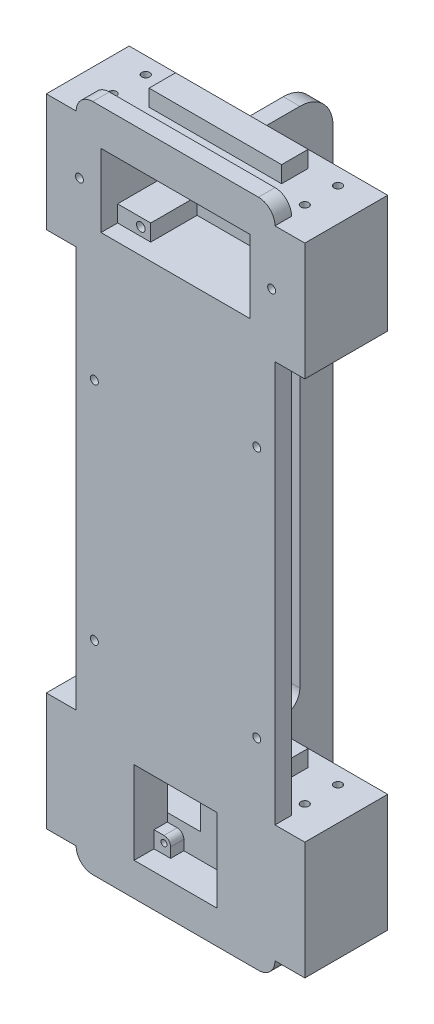
SolidWorks part; units mm, degrees
ref_plane "前视基准面" through (0, 0, 0) normal (0, 0, 1) x (1, 0, 0)
ref_plane "上视基准面" through (0, 0, 0) normal (0, 1, 0) x (1, 0, 0)
ref_plane "右视基准面" through (0, 0, 0) normal (1, 0, 0) x (0, 0, -1)
sketch "草图1" plane through (0, 0, 0) normal (0, 0, 1) x (1, 0, 0)
  line L1 (5, 0) -> (55, 0)
  line L2 (0, -5) -> (0, -197.05)
  line L3 (5, -202.05) -> (55, -202.05)
  line L4 (60, -5) -> (60, -197.05)
  arc A0 (0, -197.05) -> (5, -202.05) centre (5, -197.05) ccw
  arc A1 (55, -202.05) -> (60, -197.05) centre (55, -197.05) ccw
  arc A2 (60, -5) -> (55, 0) centre (55, -5) ccw
  arc A3 (0, -5) -> (5, 0) centre (5, -5) cw
  point P9 (60, -202.05)
  point P12 (60, 0)
  point P15 (0, 0)
  dimension "D3" = 5
  dimension "D1" = 202.05
  dimension "D2" = 60
extrude "凸台-拉伸1" add sketch "草图1" along normal blind 5
sketch "草图3" plane through (0, 0, 5) normal (0, 0, 1) x (1, 0, 0)
  line L0 (60, -101.025) -> (0, -101.025) construction
  line L1 (-9, -5) -> (69, -5)
  line L2 (-9, -5) -> (-9, -40.5)
  line L3 (-9, -40.5) -> (69, -40.5)
  line L4 (5, -202.05) -> (55, -202.05)
  line L5 (60, -197.05) -> (60, -5)
  line L6 (55, 0) -> (5, 0)
  line L7 (0, -5) -> (0, -197.05)
  line L8 (5, -202.05) -> (55, -202.05)
  line L9 (60, -197.05) -> (60, -5)
  line L10 (55, 0) -> (5, 0)
  line L11 (0, -5) -> (0, -197.05)
  line L12 (69, -5) -> (69, -40.5)
  line L13 (69, -197.05) -> (69, -161.55)
  line L14 (-9, -161.55) -> (69, -161.55)
  line L15 (-9, -197.05) -> (-9, -161.55)
  line L16 (-9, -197.05) -> (69, -197.05)
  arc A4 (0, -197.05) -> (5, -202.05) centre (5, -197.05) ccw
  arc A5 (55, -202.05) -> (60, -197.05) centre (55, -197.05) ccw
  arc A6 (60, -5) -> (55, 0) centre (55, -5) ccw
  arc A7 (5, 0) -> (0, -5) centre (5, -5) ccw
  arc A8 (0, -197.05) -> (5, -202.05) centre (5, -197.05) ccw
  arc A9 (55, -202.05) -> (60, -197.05) centre (55, -197.05) ccw
  arc A10 (60, -5) -> (55, 0) centre (55, -5) ccw
  arc A11 (5, 0) -> (0, -5) centre (5, -5) ccw
  point P16 (30, 0)
  point P17 (30, -5)
  line M14 (60, -197.05) -> (60, -5)
  line M18 (0, -5) -> (0, -197.05)
  dimension "D2" = 78
  dimension "D3" = 5
  dimension "D4" = 35.5
  dimension "D1" = 0
extrude "凸台-拉伸3" add sketch "草图3" against normal blind 25 contours L2 L3 L1 M18 | L3 L1 M18 M14 | L12 L1 L3 M14 | L15 L16 L11 L14 | L11 L16 L9 L14 | L9 L16 L13 L14 region at (-4.5, -22.75, 5) region at (30, -22.75, 5) region at (64.5, -22.75, 5) region at (30, -179.3, 5) region at (-4.5, -179.3, 5) region at (64.5, -179.3, 5)
sketch "草图4" plane through (0, -5, 0) normal (0, 1, 0) x (1, 0, 0)
  line L1 (10, 15) -> (50, 15)
  line L2 (10, 15) -> (10, 7)
  line L3 (10, 7) -> (50, 7)
  line L4 (50, 15) -> (50, 7)
  line L8 (0, 0) -> (60, 0)
  line L9 (60, -5) -> (69, -5)
  line L10 (60, -5) -> (69, -5)
  line L12 (69, 20) -> (-9, 20)
  line L13 (-9, 20) -> (-9, -5)
  line L16 (0, 0) -> (60, 0)
  line L18 (69, -5) -> (69, 20)
  line L19 (69, -5) -> (69, 20)
  line L20 (69, 20) -> (-9, 20)
  line L21 (-9, 20) -> (-9, -5)
  line L22 (-9, -5) -> (0, -5)
  line L23 (-9, -5) -> (0, -5)
  line L24 (60, 0) -> (60, -5)
  line L25 (60, 0) -> (60, -5)
  line L26 (0, -5) -> (0, 0)
  line L27 (0, -5) -> (0, 0)
  point P12 (30, 15)
  point P13 (30, 20)
  dimension "D2" = 8
  dimension "D3" = 5
  dimension "D4" = 40
  dimension "D1" = 0
extrude "凸台-拉伸4" add sketch "草图4" along normal blind 5 contours L4 L1 L2 L3 region at (30, -5, -11)
sketch "草图5" plane through (0, -5, 0) normal (0, 1, 0) x (1, 0, 0)
  line L0 (30, 20) -> (30, -5) construction
  line L1 (55, -5) -> (5, -5) construction
  line L6 (60, -5) -> (69, -5)
  line L7 (60, -5) -> (69, -5)
  line L8 (0, 0) -> (60, 0)
  line L12 (69, 20) -> (-9, 20)
  line L13 (-9, 20) -> (-9, -5)
  line L15 (69, -5) -> (69, 20)
  line L16 (0, 0) -> (60, 0)
  line L17 (69, -5) -> (69, 20)
  line L18 (-9, -5) -> (0, -5)
  line L19 (-9, -5) -> (0, -5)
  line L20 (69, 20) -> (-9, 20)
  line L21 (-9, 20) -> (-9, -5)
  line L22 (60, 0) -> (60, -5)
  line L23 (60, 0) -> (60, -5)
  line L24 (0, -5) -> (0, 0)
  line L25 (0, -5) -> (0, 0)
  circle A0 centre (1, 15) radius 1.2
  circle A1 centre (1, 5) radius 1.2
  circle A2 centre (59, 5) radius 1.2
  circle A3 centre (59, 15) radius 1.2
  dimension "D2" = 2.4
  dimension "D6" = 2.4
  dimension "D3" = 5
  dimension "D4" = 10
  dimension "D5" = 10
  dimension "D1" = 0
extrude "切除-拉伸1" cut sketch "草图5" against normal through all contours A0 | A1 | A3 | A2 region at (1, -5, -15) region at (1, -5, -5) region at (59, -5, -15)
sketch "草图6" plane through (0, -197.05, 0) normal (0, -1, 0) x (1, 0, 0)
  line L1 (10, -7) -> (50, -7)
  line L2 (10, -7) -> (10, -15)
  line L3 (10, -15) -> (50, -15)
  line L4 (50, -7) -> (50, -15)
  line L8 (0, 5) -> (-9, 5)
  line L9 (60, 0) -> (0, 0)
  line L10 (0, 5) -> (-9, 5)
  line L11 (-9, 5) -> (-9, -20)
  line L12 (-9, 5) -> (-9, -20)
  line L13 (-9, -20) -> (69, -20)
  line L17 (60, 0) -> (0, 0)
  line L19 (69, -20) -> (69, 5)
  line L20 (69, -20) -> (69, 5)
  line L21 (-9, -20) -> (69, -20)
  line L22 (69, 5) -> (60, 5)
  line L23 (69, 5) -> (60, 5)
  line L24 (60, 5) -> (60, 0)
  line L25 (60, 5) -> (60, 0)
  line L26 (0, 0) -> (0, 5)
  line L27 (0, 0) -> (0, 5)
  point P12 (30, -15)
  point P13 (30, -20)
  dimension "D2" = 40
  dimension "D3" = 8
  dimension "D4" = 5
  dimension "D1" = 0
extrude "凸台-拉伸5" add sketch "草图6" along normal blind 5 contours L4 L1 L2 L3 region at (30, -197.05, -11)
ref_plane "基准面1" through (30, 0, 0) normal (1, 0, 0) x (0, 0, -1)
sketch "草图7" plane through (30, 0, 0) normal (1, 0, 0) x (0, 0, -1)
  line L0 (20, -5) -> (30, -5)
  line L1 (40, -15) -> (40, -187.05)
  line L2 (30, -197.05) -> (20, -197.05)
  line L3 (20, -40) -> (25, -40)
  line L4 (20, -5) -> (20, -40.5) construction
  line L5 (30, -45) -> (30, -157.05)
  line L6 (25, -162.05) -> (20, -162.05)
  line L7 (20, -197.05) -> (20, -161.55) construction
  line L8 (20, -162.05) -> (20, -197.05)
  line L9 (20, -40) -> (20, -5)
  arc A0 (30, -157.05) -> (25, -162.05) centre (25, -157.05) cw
  arc A1 (25, -40) -> (30, -45) centre (25, -45) cw
  arc A2 (30, -5) -> (40, -15) centre (30, -15) cw
  arc A3 (40, -187.05) -> (30, -197.05) centre (30, -187.05) cw
  point P18 (30, -40)
  point P21 (40, -5)
  dimension "D3" = 5
  dimension "D6" = 10
  dimension "D1" = 10
  dimension "D2" = 20
  dimension "D4" = 35
  dimension "D5" = 35
extrude "凸台-拉伸6" add sketch "草图7" along normal mid plane 5
sketch "草图8" plane through (0, -161.55, 0) normal (0, 1, 0) x (1, 0, 0)
  line L1 (10, 15) -> (50, 15)
  line L2 (10, 15) -> (10, 7)
  line L3 (10, 7) -> (50, 7)
  line L4 (50, 15) -> (50, 7)
  line L8 (0, 0) -> (60, 0)
  line L9 (60, 0) -> (60, -5)
  line L10 (60, -5) -> (69, -5)
  line L11 (69, -5) -> (69, 20)
  line L12 (69, 20) -> (-9, 20)
  line L13 (-9, 20) -> (-9, -5)
  line L14 (-9, -5) -> (0, -5)
  line L15 (0, -5) -> (0, 0)
  line L16 (0, 0) -> (60, 0)
  line L17 (60, 0) -> (60, -5)
  line L18 (60, -5) -> (69, -5)
  line L19 (69, -5) -> (69, 20)
  line L20 (69, 20) -> (-9, 20)
  line L21 (-9, 20) -> (-9, -5)
  line L22 (-9, -5) -> (0, -5)
  line L23 (0, -5) -> (0, 0)
  point P12 (30, 15)
  point P13 (30, 20)
  dimension "D2" = 40
  dimension "D3" = 8
  dimension "D4" = 5
  dimension "D1" = 0
extrude "凸台-拉伸7" add sketch "草图8" along normal blind 5 contours L4 L1 L2 L3 region at (30, -161.55, -11)
sketch "草图17" plane through (0, -40.5, 0) normal (0, -1, 0) x (1, 0, 0)
  line L0 (-9, -20) -> (69, -20) construction
  line L1 (10, -7) -> (50, -7)
  line L2 (10, -7) -> (10, -15)
  line L3 (10, -15) -> (50, -15)
  line L4 (50, -7) -> (50, -15)
  line L5 (69, -20) -> (69, 5) construction
  point P6 (30, -15)
  dimension "D1" = 5
  dimension "D2" = 8
  dimension "D3" = 40
  dimension "D4" = 39
extrude "凸台-拉伸12" add sketch "草图17" along normal blind 5
sketch "草图18" plane through (0, 0, 5) normal (0, 0, 1) x (1, 0, 0)
  line L0 (-9, -197.05) -> (-9, -161.55) construction
  line L1 (17.5, -167.05) -> (42.5, -167.05)
  line L2 (17.5, -167.05) -> (17.5, -192.05)
  line L3 (17.5, -192.05) -> (42.5, -192.05)
  line L4 (42.5, -167.05) -> (42.5, -192.05)
  line L5 (60, -197.05) -> (69, -197.05) construction
  dimension "D1" = 25
  dimension "D2" = 25
  dimension "D3" = 26.5
  dimension "D4" = 5
extrude "切除-拉伸3" cut sketch "草图18" against normal blind 6
sketch "草图21" plane through (0, 0, 5) normal (0, 0, 1) x (1, 0, 0)
  line L0 (17.5, -187.05) -> (20.5, -187.05)
  line L1 (17.5, -167.05) -> (17.5, -192.05) construction
  line L2 (22.5, -189.05) -> (22.5, -192.05)
  line L3 (17.5, -192.05) -> (42.5, -192.05) construction
  line L4 (22.5, -192.05) -> (37.5, -192.05)
  line L5 (37.5, -192.05) -> (37.5, -189.05)
  line L6 (39.5, -187.05) -> (42.5, -187.05)
  line L7 (42.5, -192.05) -> (42.5, -167.05) construction
  line L8 (42.5, -187.05) -> (42.5, -172.05)
  line L9 (42.5, -172.05) -> (39.5, -172.05)
  line L10 (37.5, -170.05) -> (37.5, -167.05)
  line L11 (42.5, -167.05) -> (17.5, -167.05) construction
  line L12 (37.5, -167.05) -> (22.5, -167.05)
  line L13 (22.5, -167.05) -> (22.5, -170.05)
  line L14 (20.5, -172.05) -> (17.5, -172.05)
  line L15 (17.5, -172.05) -> (17.5, -187.05)
  circle A0 centre (20.5, -170.05) radius 0.9
  circle A1 centre (39.5, -170.05) radius 0.9
  circle A2 centre (39.5, -189.05) radius 0.9
  circle A3 centre (20.5, -189.05) radius 0.9
  arc A4 (22.5, -170.05) -> (20.5, -172.05) centre (20.5, -170.05) cw
  arc A5 (37.5, -170.05) -> (39.5, -172.05) centre (39.5, -170.05) ccw
  arc A6 (20.5, -187.05) -> (22.5, -189.05) centre (20.5, -189.05) cw
  arc A7 (39.5, -187.05) -> (37.5, -189.05) centre (39.5, -189.05) ccw
  point P26 (22.5, -172.05)
  point P33 (37.5, -172.05)
  point P36 (22.5, -187.05)
  point P39 (37.5, -187.05)
  dimension "D9" = 3
  dimension "D11" = 2
  dimension "D12" = 2
  dimension "D13" = 2
  dimension "D14" = 2
  dimension "D15" = 1.8
  dimension "D1" = 5
  dimension "D2" = 5
  dimension "D3" = 5
  dimension "D4" = 5
  dimension "D5" = 5
  dimension "D6" = 5
  dimension "D7" = 5
  dimension "D8" = 5
  dimension "D10" = 3
extrude "切除-拉伸4" cut sketch "草图21" against normal blind 10
sketch "草图22" plane through (0, 0, 5) normal (0, 0, 1) x (1, 0, 0)
  line L0 (-9, -161.55) -> (0, -161.55) construction
  line L2 (0, -40.5) -> (0, -161.55) construction
  line L3 (60, -161.55) -> (69, -161.55) construction
  line L4 (60, -161.55) -> (60, -40.5) construction
  line L7 (-9, -40.5) -> (0, -40.5) construction
  line L8 (60, -40.5) -> (69, -40.5) construction
  circle A0 centre (5.5, -140.55) radius 1.2
  circle A1 centre (54.5, -141.55) radius 1.2
  circle A2 centre (5.5, -72.55) radius 1.2
  circle A3 centre (54.5, -65.55) radius 1.2
  circle A8 centre (1, -22) radius 1.2
  circle A9 centre (59, -22) radius 1.2
  dimension "D1" = 2.4
  dimension "D2" = 2.4
  dimension "D3" = 2.4
  dimension "D4" = 2.4
  dimension "D5" = 18.5
  dimension "D6" = 18.5
  dimension "D7" = 2.4
  dimension "D8" = 2.4
  dimension "D18" = 1
  dimension "D9" = 21
  dimension "D10" = 5.5
  dimension "D11" = 20
  dimension "D12" = 5.5
  dimension "D13" = 5.5
  dimension "D14" = 5.5
  dimension "D15" = 89
  dimension "D16" = 96
  dimension "D17" = 1
extrude "切除-拉伸5" cut sketch "草图22" against normal blind 10
sketch "草图23" plane through (0, 0, 5) normal (0, 0, 1) x (1, 0, 0)
  line L0 (-9, -40.5) -> (0, -40.5) construction
  line L1 (52.5, -33) -> (7.5, -33)
  line L3 (52.5, -11) -> (7.5, -11)
  line L4 (7.5, -33) -> (7.5, -11)
  line L5 (0, -40.5) -> (0, -161.55) construction
  line L6 (52.5, -33) -> (52.5, -11)
  dimension "D1" = 45
  dimension "D2" = 22
  dimension "D3" = 7.5
  dimension "D4" = 7.5
extrude "切除-拉伸6" cut sketch "草图23" against normal blind 5
sketch "草图25" plane through (0, 0, 0) normal (0, 0, 1) x (1, 0, 0)
  line L0 (52.5, -33) -> (52.5, -16)
  line L1 (52.5, -33) -> (52.5, -11) construction
  line L2 (52.5, -16) -> (42.5, -16)
  line L3 (42.5, -16) -> (42.5, -11)
  line L4 (52.5, -11) -> (7.5, -11) construction
  line L5 (42.5, -11) -> (7.5, -11)
  line L6 (7.5, -11) -> (7.5, -28)
  line L7 (7.5, -11) -> (7.5, -33) construction
  line L8 (7.5, -28) -> (17.5, -28)
  line L9 (17.5, -28) -> (17.5, -33)
  line L10 (7.5, -33) -> (52.5, -33) construction
  line L11 (17.5, -33) -> (52.5, -33)
  line L13 (7.5, -33) -> (52.5, -33) construction
  circle A0 centre (45.5, -13.5) radius 1.3
  circle A1 centre (14.5, -30.5) radius 1.3
  dimension "D5" = 2.6
  dimension "D8" = 2.6
  dimension "D1" = 5
  dimension "D2" = 10
  dimension "D3" = 3
  dimension "D4" = 2.5
  dimension "D6" = 5
  dimension "D7" = 10
  dimension "D9" = 3
  dimension "D10" = 2.5
extrude "切除-拉伸7" cut sketch "草图25" against normal blind 14
sketch "草图26" plane through (0, 0, -20) normal (0, 0, -1) x (-1, 0, 0)
  line L0 (-32.5, -162.05) -> (-32.5, -197.05) construction
  line L1 (-32.5, -172.55) -> (-50, -172.55)
  line L2 (-32.5, -172.55) -> (-32.5, -184.55)
  line L3 (-32.5, -184.55) -> (-50, -184.55)
  line L4 (-50, -172.55) -> (-50, -184.55)
  line L6 (-32.5, -197.05) -> (-69, -197.05) construction
  line L7 (-32.5, -5) -> (-32.5, -40) construction
  line L8 (-32.5, -16) -> (-50, -16)
  line L9 (-32.5, -16) -> (-32.5, -28)
  line L10 (-32.5, -28) -> (-50, -28)
  line L11 (-50, -16) -> (-50, -28)
  line L12 (9, -40.5) -> (-69, -40.5) construction
  dimension "D1" = 17.5
  dimension "D2" = 12
  dimension "D3" = 12.5
  dimension "D4" = 17.5
  dimension "D5" = 12
  dimension "D6" = 12.5
extrude "切除-拉伸8" cut sketch "草图26" against normal blind 15
ref_plane "基准面16" through (30, 0, 0) normal (1, 0, 0) x (0, 0, -1)
mirror "镜向1" about plane through (30, 0, 0) normal (1, 0, 0) of "切除-拉伸8"
